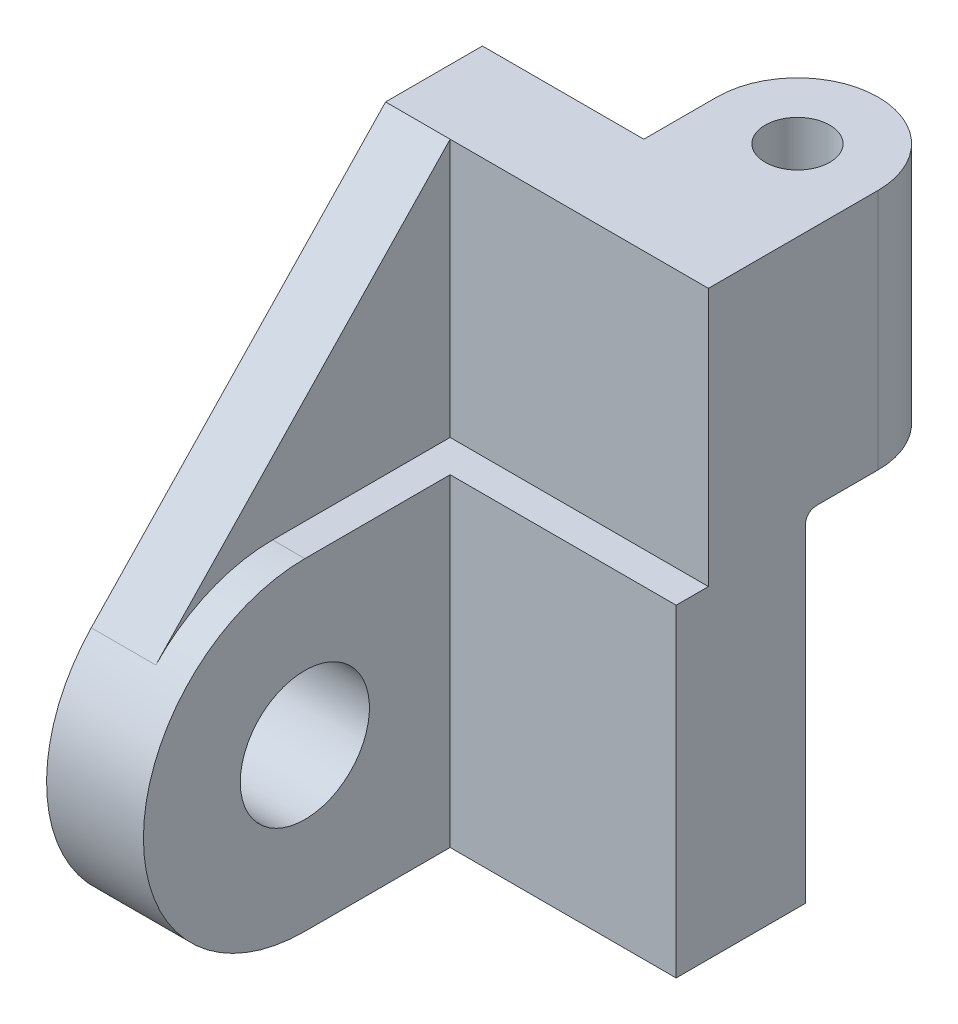
SolidWorks part; units mm, degrees
note: The reader was unsure of these and kept them because the rebuilt part matched: shared geometry of "Sketch1<3>", "Sketch1<4>".
ref_plane "Front Plane" through (0, 0, 0) normal (0, 0, 1) x (1, 0, 0)
ref_plane "Top Plane" through (0, 0, 0) normal (0, 1, 0) x (1, 0, 0)
ref_plane "Right Plane" through (0, 0, 0) normal (1, 0, 0) x (0, 0, -1)
sketch "Sketch1" plane through (0, 0, 0) normal (1, 0, 0) x (0, 0, -1)
  line L0 (0, 0) -> (0, 114.3)
  line L1 (0, 0) -> (-25.4, 0)
  line L2 (-25.4, 0) -> (-25.4, 63.5)
  line L3 (-19.05, 114.3) -> (0, 114.3)
  line L4 (-25.4, 63.5) -> (-19.05, 63.5)
  line L5 (-19.05, 63.5) -> (-19.05, 114.3)
  line L6 (-53.975, 0) -> (-25.4, 0)
  line L7 (-53.975, 63.5) -> (-25.4, 63.5)
  line L9 (-76.9378, 53.6766) -> (-19.05, 114.3)
  line L10 (0, 114.3) -> (31.75, 114.3)
  line L11 (0, 114.3) -> (0, 66.675)
  line L12 (0, 66.675) -> (31.75, 66.675)
  line L13 (31.75, 114.3) -> (31.75, 66.675)
  arc A0 (-53.975, 63.5) -> (-53.975, 0) centre (-53.975, 31.75) ccw
  circle A1 centre (-53.975, 31.75) radius 12.7
  point P5 (-25.4, 31.75)
  dimension "D4" = 63.5
  dimension "D6" = 25.4
  dimension "D1" = 114.3
  dimension "D2" = 25.4
  dimension "D3" = 63.5
  dimension "D5" = 28.575
  dimension "D7" = 19.05
  dimension "D8" = 47.625
  dimension "D9" = 31.75
extrude "Boss-Extrude1" add sketch "Sketch1" along normal blind 63.5
extrude "Boss-Extrude2" add sketch "Sketch1<3>" along normal blind 19.05 contours L7 A0 L6 L2 A1
sketch "Sketch1<3>" plane through (0, 0, 0) normal (1, 0, 0) x (0, 0, -1) same geometry as "Sketch1"
extrude "Boss-Extrude3" add sketch "Sketch1<4>" along normal blind 12.7 contours A0 L7 L4 L5 L9
sketch "Sketch1<4>" plane through (0, 0, 0) normal (1, 0, 0) x (0, 0, -1) same geometry as "Sketch1"
sketch "Sketch2" plane through (0, 0, 0) normal (0, 0, -1) x (-1, 0, 0)
  line L0 (-63.5, 66.675) -> (-31.75, 66.675)
  line L1 (-63.5, 0) -> (-63.5, 114.3) construction
  line L2 (-31.75, 66.675) -> (-31.75, 114.3)
  line L3 (-63.5, 114.3) -> (0, 114.3) construction
  line L4 (-31.75, 114.3) -> (-63.5, 114.3)
  line L5 (-63.5, 114.3) -> (-63.5, 66.675)
  dimension "D1" = 47.625
  dimension "D2" = 31.75
extrude "Boss-Extrude4" add sketch "Sketch2" along normal blind 31.75
sketch "Sketch3" plane through (0, 114.3, 0) normal (0, 1, 0) x (1, 0, 0)
  line L0 (31.75, 14.3417) -> (31.75, 31.75)
  line L1 (31.75, 31.75) -> (63.5, 31.75)
  line L2 (63.5, 31.75) -> (63.5, 14.3417)
  circle A0 centre (47.625, 14.3417) radius 6.35
  circle A1 centre (47.625, 14.3417) radius 15.875
  line M4 (63.5, -19.05) -> (63.5, 31.75)
  line M5 (63.5, 31.75) -> (31.75, 31.75)
  line M6 (31.75, 31.75) -> (31.75, 0)
  dimension "D1" = 12.7
  dimension "D2" = 31.75
  dimension "D3" = 17.4083
  dimension "D4" = 17.4083
extrude "Cut-Extrude1" cut sketch "Sketch3" against normal through all contours A1 M4 M5 M6 | A0
fillet "Fillet1" radius 2.54 1 edges
